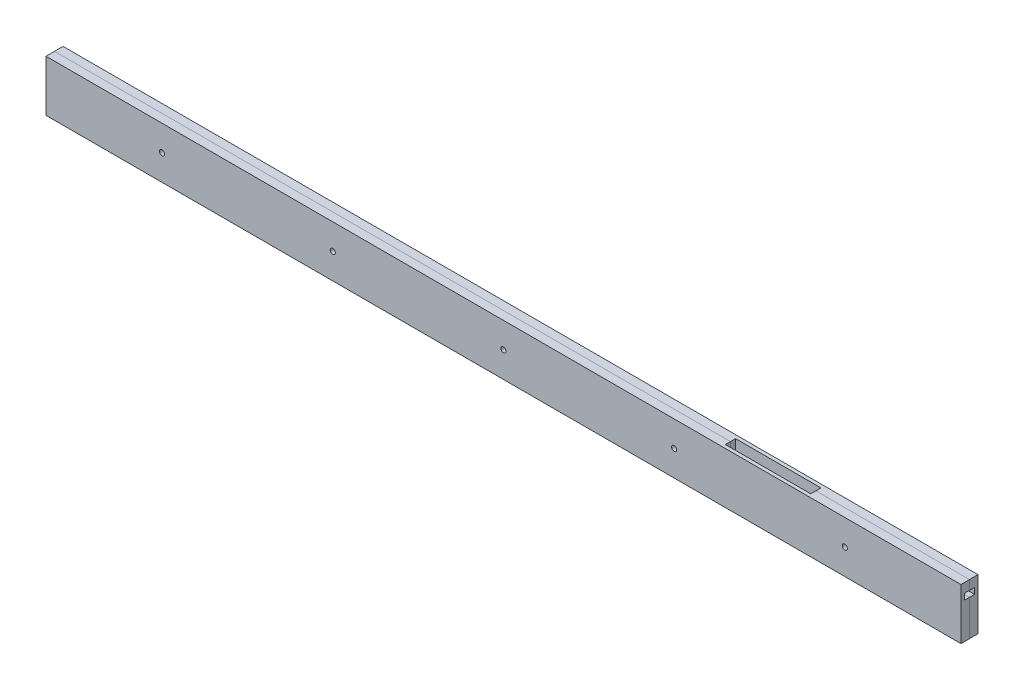
SolidWorks part; units mm, degrees
material "Настроенная пользователем пластмасса"
ref_plane "Спереди" through (0, 0, 0) normal (0, 0, 1) x (1, 0, 0)
ref_plane "Сверху" through (0, 0, 0) normal (0, 1, 0) x (1, 0, 0)
ref_plane "Справа" through (0, 0, 0) normal (1, 0, 0) x (0, 0, -1)
sketch "Эскиз1" plane through (0, 0, 0) normal (0, 0, 1) x (1, 0, 0)
  line L1 (-536, -30) -> (536, -30)
  line L2 (-536, -30) -> (-536, 30)
  line L3 (-536, 30) -> (536, 30)
  line L4 (536, -30) -> (536, 30)
  line L5 (0, 30) -> (0, -30) construction
  line L6 (-536, 0) -> (536, 0) construction
  point P0 (0, 0)
  dimension "D1" = 60
  dimension "D2" = 1072
extrude "Бобышка-Вытянуть1" add sketch "Эскиз1" along normal mid plane 10
sketch "Эскиз2" plane through (0, 0, 5) normal (0, 0, 1) x (1, 0, 0)
  line L1 (-292.5, 19) -> (256, 19)
  line L3 (-292.5, 12) -> (256, 12)
  line L4 (536, 19) -> (536, 12)
  line L5 (536, -30) -> (536, 30) construction
  line L6 (536, 30) -> (-536, 30) construction
  line L7 (-536, -30) -> (536, -30) construction
  line L8 (256, 30) -> (356, 30)
  line L9 (256, 30) -> (256, 19)
  line L10 (256, -30) -> (356, -30)
  line L11 (356, 30) -> (356, 19)
  line L12 (-536, 30) -> (-536, -30) construction
  line L13 (356, 19) -> (536, 19)
  line L14 (256, 12) -> (256, -30)
  line L15 (356, 12) -> (536, 12)
  line L16 (356, 12) -> (356, -30)
  arc A0 (-292.5, 12) -> (-292.5, 19) centre (-292.5, 15.5) cw
  dimension "D1" = 240
  dimension "D2" = 11
  dimension "D3" = 7
  dimension "D4" = 100
  dimension "D5" = 180
extrude "Вырез-Вытянуть1" cut sketch "Эскиз2" against normal blind 6
sketch "Эскиз3" plane through (0, 0, 5) normal (0, 0, 1) x (1, 0, 0)
  line L0 (356, -30) -> (536, -30) construction
  line L3 (400, 0) -> (536, 0) construction
  line L4 (536, -30) -> (536, 12) construction
  circle A0 centre (400, 0) radius 3
  dimension "D1" = 6
  dimension "D2" = 30
  dimension "D4" = 136
extrude "Вырез-Вытянуть2" cut sketch "Эскиз3" against normal through all
chamfer "Фаска1" distance 2 angle 45 1 edges at (403, 0, 5)
pattern_linear "Линейный массив1" count 5 spacing 200 along (-1, 0, 0) of "Вырез-Вытянуть2", "Фаска1"
mirror "Зеркальное отражение1" about plane through (0, 0, 5) normal (0, 0, -1) of bodies 107 104
